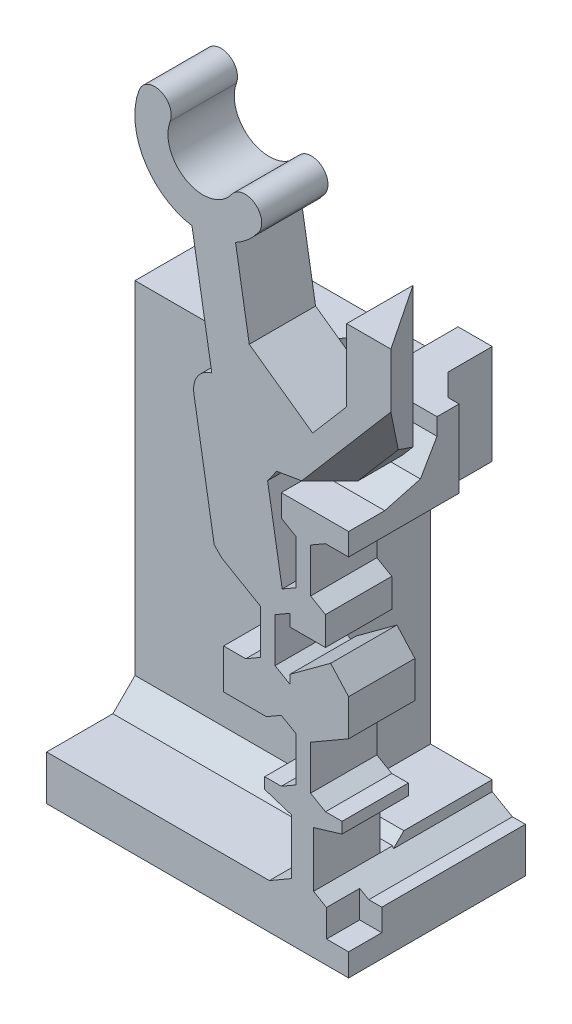
SolidWorks part; units mm, degrees
ref_plane "Front Plane" through (0, 0, 0) normal (0, 0, 1) x (1, 0, 0)
ref_plane "Top Plane" through (0, 0, 0) normal (0, 1, 0) x (1, 0, 0)
ref_plane "Right Plane" through (0, 0, 0) normal (1, 0, 0) x (0, 0, -1)
sketch "Sketch-SkeletonConfigUp" plane through (0, 0, 0) normal (0, 0, 1) x (1, 0, 0)
  line L0 (0, 0) -> (0, -50000) construction
  line L1 (0, 0) -> (4.5811, 6.2164) construction
  line L2 (9.8143, 13.3177) -> (4.5811, 13.945) construction
  line L3 (4.5811, 13.945) -> (2.9713, 10.4094) construction
  line L4 (2.9713, 10.4094) -> (4.5811, 6.2164) construction
  line L5 (4.5811, 13.945) -> (6.2429, 19.1409) construction
  line L6 (2.9713, 10.4094) -> (0.0405, 27.8193) construction
  line L7 (4.5811, 6.2164) -> (9.8143, 13.3177) construction
  line L8 (-587.3593, -797.0242) -> (9.8143, 13.3177) construction
  dimension "D2" = 7.7221
  dimension "D3" = 8.8212
  dimension "D4" = 5.2707
  dimension "D5" = 119.553
  dimension "D6" = 3.8848
  dimension "D7" = 5.4552
  dimension "D8" = 17.6549
  dimension "D9" = 4.4914
  dimension "D10" = 6.745
  dimension "D11" = 145.964
  dimension "D12" = 143.612
sketch "Sketch-SkeletonConfigDown" plane through (0, 0, 0) normal (0, 0, 1) x (1, 0, 0)
  line L0 (0, 0) -> (0, -50000) construction
  line L1 (0, 0) -> (4.5811, 6.2164) construction
  line L2 (9.8143, 13.3177) -> (4.5811, 13.945) construction
  line L3 (4.5811, 13.945) -> (6.1909, 10.4094) construction
  line L4 (6.1909, 10.4094) -> (4.5811, 6.2164) construction
  line L5 (4.5811, 13.945) -> (1.753, 18.6098) construction
  line L6 (6.1909, 10.4094) -> (-8.8652, 19.6294) construction
  line L7 (4.5811, 6.2164) -> (9.8143, 13.3177) construction
  line L8 (-589.9357, -800.5203) -> (9.8143, 13.3177) construction
  dimension "D2" = 7.7221
  dimension "D3" = 8.8212
  dimension "D4" = 5.2707
  dimension "D5" = 119.553
  dimension "D6" = 3.8848
  dimension "D7" = 5.4552
  dimension "D8" = 17.6549
  dimension "D9" = 4.4914
  dimension "D10" = 6.745
  dimension "D11" = 145.964
  dimension "D1" = 143.612
ref_plane "Plane-Cam Base" through (9.128, 0, 0) normal (1, 0, 0) x (0, 0, -1)
ref_plane "Plane-Down-to-Up Derailleur Clearance" through (6.628, 0, 0) normal (1, 0, 0) x (0, 0, -1)
ref_plane "Plane-Cam Cavity Roof" through (5.128, 0, 0) normal (1, 0, 0) x (0, 0, -1)
sketch "Sketch-SwitchBossUp" plane through (0, 0, 0) normal (0, 0, 1) x (1, 0, 0)
  line L0 (3.5811, 11.4759) -> (3.5811, 12.945) construction
  line L2 (6.5405, 21.1774) -> (6.5405, 24.4384)
  line L3 (6.5405, 24.4384) -> (8.5405, 24.4384)
  line L4 (8.5405, 24.4384) -> (8.5405, 20.4384)
  line L5 (5.5811, 12.5552) -> (5.5811, 11.263)
  line L7 (1.5115, 25.1048) -> (2.5464, 18.9575)
  line L8 (-0.4607, 24.7728) -> (0.4359, 19.4465)
  line L9 (2.9713, 10.4094) -> (0.0405, 27.8193) construction
  line L11 (-0.0396, 22.2712) -> (1.9326, 22.6032) construction
  line L15 (6.628, -23.7286) -> (6.628, 23.7286) construction
  line L16 (2.9713, 10.4094) -> (4.5811, 6.2164) construction
  line L17 (3.5811, 12.945) -> (3.5811, 14.945) construction
  line L18 (5.5811, 12.945) -> (5.5811, 14.945) construction
  line L19 (4.2561, 13.945) -> (4.9061, 13.945) construction
  line L20 (3.5811, 14.945) -> (5.5811, 14.945) construction
  line L21 (3.5811, 12.945) -> (5.5811, 12.945) construction
  line L22 (4.5811, 12.945) -> (4.5811, 14.945) construction
  line L23 (4.5811, 6.2164) -> (8.5405, 7.1023) construction
  line L24 (1.9713, 9.4094) -> (1.9713, 11.4094) construction
  line L25 (3.9713, 9.4094) -> (3.9713, 11.4094) construction
  line L26 (3.9713, 9.4094) -> (1.9713, 9.4094) construction
  line L27 (1.9713, 11.4094) -> (3.9713, 11.4094) construction
  line L28 (3.5811, 7.2164) -> (5.5811, 7.2164) construction
  line L29 (3.5811, 7.2164) -> (3.5811, 5.2164) construction
  line L30 (5.5811, 7.2164) -> (5.5811, 5.2164) construction
  line L31 (3.5811, 5.2164) -> (5.5811, 5.2164) construction
  line L32 (4.9061, 6.2164) -> (4.2561, 6.2164) construction
  line L40 (3.2963, 10.4094) -> (2.6463, 10.4094) construction
  line L43 (2.874, 4.5093) -> (0.7934, 4.5093) construction
  line L46 (5.0405, 1.437) -> (5.0405, 3.937)
  line L51 (4.9929, 19.3693) -> (2.5464, 18.9575)
  line L66 (0.0405, 27.8193) -> (0.0405, 50027.8193) construction
  line L74 (0.5455, 12.7717) -> (-0.3728, 18.2264)
  line L75 (0.3841, 13.7302) -> (2.3564, 14.0622) construction
  line L76 (5.5811, 11.263) -> (5.5811, 12.5552) construction
  line L77 (5.5811, 7.6061) -> (6.628, 8.2105)
  line L80 (5.8152, 10.763) -> (6.628, 9.8603)
  line L81 (8.5405, 1033.6218) -> (8.5405, 20.4384) construction
  line L82 (2.5464, 18.9575) -> (3.5585, 12.945) construction
  line L83 (3.6203, 12.5779) -> (2.8784, 16.9852)
  line L84 (2.8784, 16.9852) -> (6.0405, 17.5175)
  line L85 (6.9307, 9.5241) -> (8.5405, 7.7363) construction
  line L88 (3.5811, 16.3347) -> (6.8573, 16.3347)
  line L92 (3.7762, 8.3129) -> (6.9307, 9.5241) construction
  line L93 (6.3311, 4.3267) -> (5.0405, 3.937)
  line L95 (2.5464, 18.9575) -> (2.8784, 16.9852) construction
  line L96 (2.7124, 17.9713) -> (8.5405, 18.9524) construction
  line L97 (2.7124, 17.9713) -> (1.7262, 17.8053) construction
  line L98 (1.9713, 9.0197) -> (0.9713, 9.0197)
  line L99 (0.9713, 9.0197) -> (0.9713, 7.2164)
  line L100 (0.9713, 7.2164) -> (2.9061, 7.2164)
  line L101 (4.5811, 6.2164) -> (6.9307, 9.5241) construction
  line L103 (0.0405, 27.8193) -> (1.9448, 26.4638) construction
  line L104 (6.9307, 9.5241) -> (8.5405, 7.7363) construction
  line L106 (13.4416, 14.945) -> (5.5811, 14.945) construction
  line L107 (1.9713, 9.4094) -> (1.9713, 9.0197) construction
  line L109 (0.0405, 27.8193) -> (-2.1498, 28.6358) construction
  line L110 (8.5405, 20.4384) -> (6.0405, 17.5175)
  line L111 (6.628, 9.8603) -> (6.628, 8.2105)
  line L112 (6.628, 9.8603) -> (6.9307, 9.5241) construction
  line L113 (2.8311, 4.8267) -> (2.8311, 4.3267)
  line L114 (7.3693, 7.7363) -> (7.3563, 7.7363) construction
  line L115 (6.8573, 16.3347) -> (13.4416, 16.3347)
  line L116 (13.4416, 16.3347) -> (13.4416, -1.1653)
  line L117 (13.4416, -1.1653) -> (5.0405, -1.1653)
  line L119 (10.4375, 14.0252) -> (10.4375, 2.1692)
  line L121 (5.0405, -1.1653) -> (5.0405, 1.437) construction
  line L122 (8.237, 12.8031) -> (10.8393, 12.8031) construction
  line L123 (10.8393, 12.8031) -> (13.4416, 12.8031) construction
  line L124 (10.4375, 2.1692) -> (9.128, 0.8597)
  line L125 (8.5405, 7.5847) -> (13.4416, 7.5847) construction
  line L127 (5.5811, 15.3347) -> (5.5811, 14.945) construction
  line L130 (6.0405, 0.8597) -> (9.128, 0.8597)
  line L132 (2.8311, 4.3267) -> (4.0405, 3.937)
  line L133 (2.9713, 10.4094) -> (6.1909, 10.4094) construction
  line L134 (4.5811, 10.4094) -> (4.5811, 13.945) construction
  line L135 (4.5811, 10.4094) -> (4.5811, 6.2164) construction
  line L136 (0.8973, 12.4192) -> (0.5455, 12.7717)
  line L137 (3.9713, 9.4094) -> (5.5811, 7.2164) construction
  line L139 (5.8152, 10.763) -> (3.9713, 9.4094)
  line L140 (4.0405, 3.937) -> (4.0405, 1.437)
  line L141 (4.0405, 1.437) -> (3.0405, 0.8597)
  line L142 (3.0405, 0.8597) -> (3.0405, -1.1653)
  line L143 (8.5405, 20.4384) -> (8.5405, 18.9524) construction
  line L145 (8.5405, 17.9384) -> (8.5405, -49992.0368) construction
  line L147 (5.5811, 11.263) -> (5.5811, 12.5552) construction
  line L149 (6.3311, 4.8267) -> (6.3311, 4.3267)
  line L150 (3.0405, -1.1653) -> (5.0405, -1.1653)
  line L151 (4.0405, 3.937) -> (5.0405, 3.937) construction
  line L152 (4.2561, 14.945) -> (4.2561, 12.945)
  line L153 (4.9061, 14.945) -> (4.9061, 12.945)
  line L155 (4.2561, 14.945) -> (3.5811, 15.3347)
  line L156 (4.9061, 14.945) -> (5.5811, 15.3347)
  line L157 (3.5811, 16.3347) -> (3.5811, 15.3347)
  line L158 (5.5811, 15.3347) -> (9.128, 15.3347)
  line L162 (3.2963, 11.4094) -> (3.2963, 9.4094)
  line L164 (2.6463, 11.4094) -> (2.6463, 9.4094)
  line L169 (4.2561, 7.2164) -> (4.2561, 5.2164)
  line L170 (4.9061, 5.2164) -> (4.9061, 7.2164)
  line L175 (4.2561, 7.2164) -> (3.5811, 7.6061)
  line L176 (4.9061, 7.2164) -> (5.5811, 7.6061)
  line L177 (5.5811, 7.2164) -> (5.5811, 7.6061) construction
  line L179 (4.2561, 5.2164) -> (3.5811, 4.8267)
  line L180 (3.5811, 5.2164) -> (3.5811, 4.8267) construction
  line L181 (3.5811, 4.8267) -> (2.8311, 4.8267)
  line L183 (4.9061, 5.2164) -> (5.5811, 4.8267)
  line L184 (5.5811, 5.2164) -> (5.5811, 4.8267) construction
  line L186 (9.128, -23.7286) -> (9.128, 23.7286) construction
  line L187 (2.6463, 9.4094) -> (1.9713, 9.0197)
  line L188 (3.2963, 9.4094) -> (3.9713, 9.0197)
  line L189 (3.2963, 11.4094) -> (3.9713, 11.7991)
  line L190 (2.6463, 11.4094) -> (0.8973, 12.4192)
  line L191 (3.9713, 11.4094) -> (3.9713, 11.7991) construction
  line L192 (3.9713, 11.7991) -> (3.9713, 11.263)
  line L193 (4.9061, 12.945) -> (5.5811, 12.5552)
  line L194 (4.2561, 12.945) -> (3.6203, 12.5779)
  line L195 (3.9713, 11.263) -> (5.5811, 11.263)
  line L196 (3.9713, 9.4094) -> (3.9713, 9.0197)
  line L197 (3.5811, 7.2164) -> (3.5811, 7.6061) construction
  line L199 (3.5811, 7.6061) -> (2.9061, 7.2164)
  line L200 (5.5811, 4.8267) -> (6.3311, 4.8267)
  line L201 (2.8311, 4.3267) -> (2.8311, 3.937) construction
  line L202 (2.8311, 3.937) -> (4.0405, 3.937) construction
  line L203 (10.4375, 14.0252) -> (9.128, 15.3347)
  line L204 (4.0405, 1.437) -> (3.0405, 1.437) construction
  line L205 (3.0405, 1.437) -> (3.0405, 0.8597) construction
  line L206 (5.0405, 1.437) -> (6.0405, 0.8597)
  line L207 (8.5405, 18.9524) -> (8.5405, 17.9384) construction
  line L208 (6.0405, 17.5175) -> (8.5405, 17.9384) construction
  line L209 (8.5405, 20.4384) -> (8.5405, 17.9384) construction
  line L210 (6.5405, 21.1774) -> (4.9929, 19.3693)
  arc A0 (1.5115, 25.1048) -> (2.5558, 26.0289) centre (0.0405, 27.8193) ccw
  arc A1 (-0.4607, 24.7728) -> (-2.8525, 28.8978) centre (0.0405, 27.8193) cw
  arc A2 (-2.8525, 28.8978) -> (-1.447, 28.3738) centre (-2.1498, 28.6358) cw
  arc A3 (2.5558, 26.0289) -> (1.3338, 26.8987) centre (1.9448, 26.4638) ccw
  arc A4 (-1.447, 28.3738) -> (1.3338, 26.8987) centre (0.0405, 27.8193) ccw
  arc A5 (3.5811, 12.945) -> (3.5811, 14.945) centre (3.1778, 13.945) ccw construction
  arc A6 (5.5811, 12.945) -> (5.5811, 14.945) centre (5.9843, 13.945) cw construction
  arc A7 (2.5293, 9.921) -> (1.9713, 11.4094) centre (1.568, 10.4094) ccw construction
  arc A8 (3.9713, 11.4094) -> (3.9713, 9.4094) centre (4.3745, 10.4094) ccw construction
  arc A9 (3.5811, 7.2164) -> (3.5811, 5.2164) centre (3.1779, 6.2164) cw construction
  arc A10 (5.5811, 7.2164) -> (5.5811, 5.2164) centre (5.9844, 6.2164) ccw construction
  arc A19 (-0.3728, 18.2264) -> (0.4359, 19.4465) centre (0.6836, 18.4042) cw
  circle A28 centre (0.0405, 27.8193) radius 2.3375 construction
  arc A29 (1.9713, 9.4094) -> (2.5293, 9.921) centre (1.568, 10.4094) ccw construction
  point P53 (4.5811, 13.945)
  point P63 (2.9713, 10.4094)
  point P93 (0.9465, 22.4372)
  dimension "D23" = 1.5875
  dimension "D24" = 0.75
  dimension "D2" = 2
  dimension "D5" = 2
  dimension "D6" = 0.65
  dimension "D8" = 42
  dimension "D7" = 2
  dimension "D10" = 5
  dimension "D11" = 8.5
  dimension "D14" = 7.5
  dimension "D4" = 3
  dimension "D16" = 42
  dimension "D12" = 1
  dimension "D13" = 2.5
  dimension "D25" = 120
  dimension "D26" = 120
  dimension "D27" = 120
  dimension "D28" = 120
  dimension "D29" = 120
  dimension "D30" = 120
  dimension "D31" = 120
  dimension "D32" = 120
  dimension "D33" = 120
  dimension "D34" = 120
  dimension "D35" = 120
  dimension "D36" = 120
  dimension "D17" = 0.5
  dimension "D20" = 3.5
  dimension "D21" = 1
  dimension "D18" = 45
  dimension "D9" = 17.5
  dimension "D22" = 1
  dimension "D19" = 120
  dimension "D37" = 120
  dimension "D15" = 45
  dimension "D38" = 2
  dimension "D39" = 0.5
  dimension "D40" = 60
  dimension "D41" = 1
  dimension "D42" = 45
  dimension "D43" = 120
  dimension "D44" = 2
  dimension "D45" = 2.5
  dimension "D46" = 2.5
  dimension "D47" = 4
  dimension "D48" = 2
extrude "Boss-Switch Main" add sketch "Sketch-SwitchBossUp" along normal blind 3
sketch "Sketch1" plane through (0, 0, 0) normal (0, 0, -1) x (-1, 0, 0)
  line L0 (-3.5811, 16.3347) -> (-3.5811, 15.3347) construction
  line L1 (-7.5811, -1.1653) -> (0.4122, -1.1653)
  line L2 (-7.5811, -1.1653) -> (-7.5811, 0.8597)
  line L4 (0.4122, -1.1653) -> (0.4122, 0.8597)
  line L5 (-3.5811, 18.8347) -> (-7.5811, 18.8347)
  line L10 (-7.5811, 18.8347) -> (-7.5811, 15.3347)
  line L11 (-4.0405, 1.437) -> (-5.0405, 1.437)
  line L12 (-7.5811, 15.3347) -> (-3.5811, 15.3347)
  line L13 (-4.0405, 1.437) -> (-3.0405, 0.8597)
  line L14 (-3.5811, 15.3347) -> (-3.5811, 18.8347)
  line L22 (-3.0405, -1.1653) -> (-13.4416, -1.1653) construction
  line L23 (-3.0405, 0.8597) -> (0.4122, 0.8597)
  line L24 (-5.0405, 1.437) -> (-6.0405, 0.8597)
  line L25 (-6.0405, 0.8597) -> (-7.5811, 0.8597)
  line L26 (-9.128, 15.3347) -> (-5.5811, 15.3347) construction
  dimension "D1" = 3.5
  dimension "D4" = 4
extrude "Boss-Flange Width" add sketch "Sketch1" along normal blind 5
ref_plane "Plane-Sta2Sit Groove" through (0.0405, 0, 0) normal (1, 0, 0) x (0, 0, -1)
ref_plane "Plane-Cam Outer Surface" through (-12.0395, 0, 0) normal (1, 0, 0) x (0, 0, -1)
ref_plane "Plane-FlangeTop" through (-7.0395, 0, 0) normal (1, 0, 0) x (0, 0, -1)
sketch "Sketch2" plane through (-7.0395, 0, 0) normal (1, 0, 0) x (0, 0, -1)
  line L0 (5, 15.3347) -> (0, 15.3347) construction
  line L1 (5, 17.3347) -> (1, 17.3347)
  line L2 (5, 17.3347) -> (5, 15.3347)
  line L3 (5, 15.3347) -> (1, 15.3347)
  line L4 (1, 17.3347) -> (1, 15.3347)
  line L10 (-3, -1.1653) -> (-3, 16.3347) construction
  line L11 (5, 0.8597) -> (-3, 0.8597)
  line L12 (5, 0.8597) -> (5, -1.1653)
  line L13 (5, -1.1653) -> (-3, -1.1653)
  line L14 (-3, 0.8597) -> (-3, -1.1653)
  line L15 (0, 10.4094) -> (0, 27.8193) construction
  line L17 (5, 0.8597) -> (5, -1.1653) construction
  line L18 (-3, 0.8597) -> (0, 0.8597) construction
  dimension "D1" = 1
  dimension "D2" = 2
extrude "Boss-Flange Height" add sketch "Sketch2" along normal up to surface (11.6675 mm away)
sketch "Sketch10" plane through (0, 15.3347, 0) normal (0, 1, 0) x (1, 0, 0)
  line L0 (9.128, -23.7286) -> (9.128, 23.7286) construction
  line L1 (7.5811, 5) -> (5.128, 5)
  line L2 (7.5811, 5) -> (7.5811, 2)
  line L3 (7.5811, 2) -> (5.128, 2)
  line L5 (4.628, 7) -> (4.628, 1) construction
  line L6 (3.5811, 1) -> (-7.0395, 1) construction
  line L8 (5.128, 5) -> (5.128, 2)
  dimension "D1" = 1
  dimension "D2" = 0.5
  dimension "D3" = 4.5
extrude "Cut-Up-To-Down Derailleur Clearance" cut sketch "Sketch10" along normal up to next
sketch "Sketch17" plane through (0, 15.3347, 0) normal (0, -1, 0) x (1, 0, 0)
  line L0 (5.128, -5) -> (-7.0395, -5)
  line L1 (5.128, -5) -> (3.5811, -5) construction
  line L2 (-7.0395, -5) -> (-7.0395, -1)
  line L3 (-7.0395, -1) -> (5.128, -1)
  line L4 (5.128, -1) -> (5.128, -5)
  line L5 (-7.0395, -1) -> (-7.0395, -5) construction
extrude "Boss-Flange Support" add sketch "Sketch17" along normal up to surface (14.475 mm away) up to face at (-1.9995, 0.8597, -1)
sketch "Sketch-HolePositions" plane through (0, -1.1653, 0) normal (0, -1, 0) x (1, 0, 0)
  line L0 (-7.0395, -3) -> (7.5811, -3) construction
  line L1 (7.5811, -5) -> (-7.0395, -5) construction
  line L2 (7.5811, -5) -> (7.5811, 0) construction
  line L4 (-7.0395, -22.2167) -> (-7.0395, 22.2167) construction
  line L5 (3.5811, -1) -> (3.5811, -5) construction
  point P6 (-4.0395, -3)
  point P7 (0.5811, -3)
  dimension "D1" = 3
  dimension "D2" = 3
  dimension "D3" = 2
sketch "Sketch6" plane through (0, -1.1653, 0) normal (0, -1, 0) x (-1, 0, 0)
  point P0 (4.0395, 3)
  point P3 (-0.5811, 3)
hole_wizard "Tap Drill for M2x0.4 Tap1" positions "Sketch6" profile "Sketch5" hole size "M2x0.4" standard "ANSI Metric" end condition through all
sketch "Sketch5" plane through (-4.0395, -1.1653, -3) normal (1, 0, 0) x (0, 0, -1)
  line L0 (0, 0) -> (0, 30.5511)
  line L1 (0, 30.5511) -> (0.8, 30.5511)
  line L2 (0.8, 30.5511) -> (0.8, 0)
  line L5 (0.8, 0) -> (0, 0)
  line L11 (0, -6.35) -> (0, 107.95) construction
  dimension "Thru Hole Dia." = 1.6
  dimension "Thru Hole Depth" = 30.5511
sketch "Sketch9" plane through (0, -1.1653, 0) normal (0, -1, 0) x (1, 0, 0)
  point P0 (-4.0395, -3)
  point P3 (0.5811, -3)
hole_wizard "M2 Clearance Hole2" positions "Sketch9" profile "Sketch8" hole size "M2" standard "ANSI Metric"
sketch "Sketch8" plane through (-4.0395, -1.1653, -3) normal (1, 0, 0) x (0, 0, -1)
  line L0 (0, 0) -> (0, 15.721)
  line L1 (0, 15.721) -> (1.2, 15)
  line L2 (1.2, 15) -> (1.2, 0)
  line L5 (1.2, 0) -> (0, 0)
  line L10 (0, 15.721) -> (-1.2, 15) construction
  line L11 (0, -6.35) -> (0, 107.95) construction
  dimension "Hole Dia." = 2.4
  dimension "Hole Depth" = 15
  dimension "Drill Angle" = 118
sketch "Sketch-Measurements for Derailleur Ramps" plane through (0, 0, 0) normal (0, 0, 1) x (1, 0, 0)
  line L0 (2.8784, 16.9852) -> (2.5464, 18.9575)
  line L1 (2.7124, 17.9713) -> (1.7262, 17.8053)
  line L2 (2.9713, 10.4094) -> (0.0405, 27.8193) construction
  line L3 (1.7262, 17.8053) -> (-1.8937, 15.3603)
  line L4 (6.1909, 10.4094) -> (-8.8652, 19.6294) construction
  line L5 (1.7262, 17.8053) -> (2.6012, 12.6077)
  line L6 (2.6012, 12.6077) -> (-1.8937, 15.3603)
  line L7 (-0.0837, 16.5828) -> (-0.0837, 17.8053)
  line L8 (-0.0837, 17.8053) -> (1.7262, 17.8053)
  line L9 (6.1909, 10.4094) -> (2.9713, 10.4094)
  line L10 (5.386, 8.3129) -> (3.7762, 8.3129)
  line L12 (6.1909, 10.4094) -> (4.5811, 6.2164) construction
  line L13 (4.5811, 8.3129) -> (4.5811, 8.7912)
  line L14 (4.5811, 6.2164) -> (5.386, 8.3129)
  line L15 (2.9713, 10.4094) -> (4.5811, 6.2164) construction
  line L16 (3.7762, 8.3129) -> (4.5811, 6.2164)
  line L17 (5.386, 8.3129) -> (5.386, 8.7912)
  dimension "D1" = 1.81
  dimension "D2" = 0.8049
sketch "Sketch12" plane through (0, 24.4384, 0) normal (0, 1, 0) x (1, 0, 0)
  line L0 (6.5405, 0) -> (8.5405, -3)
  line L1 (8.5405, -3) -> (8.5405, 0)
  line L2 (8.5405, 0) -> (6.5405, 0)
extrude "Cut-Up-to-Down Cantilever Slope" cut sketch "Sketch12" against normal up to next
ref_plane "Plane1" through (0, 7.1023, 0) normal (0, 1, 0) x (1, 0, 0)
sketch "Sketch-Derailleur Location" plane through (0, 7.1023, 0) normal (0, 1, 0) x (1, 0, 0)
  line L0 (8.5405, 0) -> (8.5405, -3)
  line L1 (4.0405, -3) -> (3.0405, -3) construction
  line L2 (-119237.4187, 0) -> (9.8143, 0) construction
  point P0 (8.5405, 0)
  point P8 (8.5405, -1.5)
ref_plane "Plane-Cantilever Cut" [suppressed] through (7.0848, 8.5204, -1.9058) normal (-0.6301, -0.7578, 0.1695) x (-0.7765, 0.6151, -0.1368)
sketch "Sketch14" [suppressed] plane through (7.0848, 8.5204, -1.9058) normal (-0.6301, -0.7578, 0.1695) x (-0.7765, 0.6151, -0.1368)
  line L0 (2.3023, -1.6911) -> (-0.3551, -1.6911)
  line L2 (2.3023, -4.3362) -> (2.3023, -1.6911)
  line L3 (-0.3551, -1.6911) -> (-0.3551, -4.4608)
  line L5 (-0.3551, -4.4608) -> (1.0087, -5.0843)
  line L6 (1.0087, -5.0843) -> (2.3023, -4.3362)
extrude "Cut-Down-to-Up Cantilever Slope" [suppressed] cut sketch "Sketch14" against normal up to next
sketch "Sketch16" plane through (0, 0, 0) normal (0, 0, -1) x (-1, 0, 0)
  line L0 (-7.5811, 18.8347) -> (-13.4416, 18.8347)
  line L1 (-13.4416, 18.8347) -> (-13.4416, -1.1653)
  line L2 (-13.4416, -1.1653) -> (-6.628, -1.1653)
  line L3 (-13.4416, -1.1653) -> (-5.0405, -1.1653) construction
  line L4 (-6.628, -1.1653) -> (-6.628, 5.2038)
  line L5 (-6.628, 5.2038) -> (-8.0037, 5.2038)
  line L6 (-8.0037, 5.2038) -> (-8.0037, 12.0484)
  line L7 (-8.0037, 12.0484) -> (-6.628, 12.0484)
  line L8 (-6.628, 12.0484) -> (-6.628, 17.9477)
  line L9 (-6.628, 23.7286) -> (-6.628, -23.7286) construction
  line L10 (-3.5811, 18.8347) -> (-6.5405, 18.8347) construction
  line L11 (-7.5811, 18.8347) -> (-6.628, 17.9477)
extrude "Cut-Down-to-Up Derailleur Clearance" cut sketch "Sketch16" against normal through all and the other way through all
ref_plane "Plane-Symmetry Plane" through (0, 0, 1.5) normal (0, 0, 1) x (1, 0, 0)
sketch "Sketch-Cable Center Point" plane through (0, 0, 1.5) normal (0, 0, 1) x (1, 0, 0)
  line L0 (0.0405, 27.8193) -> (0.1722, 27.0366)
  line L1 (2.9713, 10.4094) -> (0.0405, 27.8193) construction
  point P0 (0.0405, 27.8193)
  dimension "D1" = 0.7937
chamfer "Chamfer-Flange Support" distance 1.5 angle 45 1 edges at (3.5811, 17.3347, -3)
chamfer "Chamfer-Flange Support 2" distance 1 angle 45 2 edges at (5.128, 17.0847, -2) (5.128, 15.3347, -1.5)
chamfer "Chamfer-Flange Support 3" distance 1 angle 45 1 edges at (-1.9995, 0.8597, -1)
sketch "Sketch18" plane through (6.628, 0, 0) normal (1, 0, 0) x (0, 0, -1)
  line L1 (-3, -0.1403) -> (-1.5, -0.1403)
  line L2 (-3, -0.1403) -> (-3, 1.437)
  line L3 (-3, 1.437) -> (-1.5, 1.437)
  line L4 (-1.5, -0.1403) -> (-1.5, 1.437)
  line L5 (0.5774, 1.437) -> (0, 1.437) construction
  line L6 (-3, -1.1653) -> (-3, 0.8597) construction
  line L7 (-3, 0.8597) -> (5, 0.8597) construction
  dimension "D1" = 1.5
  dimension "D2" = 1
extrude "Cut-Down-to-Up Derailleur Clearance 2" cut sketch "Sketch18" against normal blind 1
sketch "Sketch19" plane through (0, 0, 0) normal (0, 0, 1) x (1, 0, 0)
  line L7 (3.5811, 18.8347) -> (6.628, 18.8347)
  line L8 (6.628, 18.8347) -> (6.628, 16.3347)
  line L9 (6.628, 16.3347) -> (3.5811, 16.3347)
  line L10 (3.5811, 16.3347) -> (3.5811, 18.8347)
  line L11 (6.628, 16.3347) -> (6.628, 17.9477) construction
extrude "Cut-Up-to-Down Cantilever Clearance" cut sketch "Sketch19" against normal up to surface (1 mm away) up to face at (1.4435, 12.7784, -1)
chamfer "Chamfer1" distance 1 angle 60 1 edges at (5.1045, 16.3347, -1) first distance on face at (5.1045, 16.3347, 1)
chamfer "Chamfer3" distance 0.75 angle 60 1 edges at (3.5811, 16.7007, -1) first distance on face at (3.5811, 16.1233, 0.6667)
chamfer "Chamfer4" distance 0.5 angle 60 1 edges at (4.205, 15.3347, -1) first distance on face at (5.1242, 15.3347, -0.0278)
chamfer "Chamfer5" distance 0.5 angle 45 1 edges at (2.8784, 16.9852, 1.5)
chamfer "Chamfer6" distance 2.5 angle 45 1 edges at (2.5464, 18.9575, 1.5)
chamfer "Chamfer7" distance 1 angle 45 1 edges at (7.2905, 18.978, 3)
sketch "Sketch22" plane through (0, 0, 0) normal (0, 0, 1) x (1, 0, 0)
  line L0 (6.628, 17.9477) -> (7.5811, 18.8347) construction
  line L1 (6.628, 18.8347) -> (7.5811, 18.8347) construction
  line L2 (6.628, 17.9477) -> (6.628, 18.8347) construction
  line L3 (6.628, 17.9477) -> (7.5811, 18.8347)
  line L4 (6.628, 18.8347) -> (7.5811, 18.8347)
  line L5 (6.628, 17.9477) -> (6.628, 18.8347)
extrude "Cut-Extrude3" cut sketch "Sketch22" against normal up to next
chamfer "Chamfer8" distance 0.5 angle 45 1 edges at (5.1045, 16.3347, 0) first distance on face at (4.2965, 17.2286, -0.5161)
sketch "Sketch23" plane through (0, 0, -1) normal (0, 0, 1) x (1, 0, 0)
  line L0 (5.128, 1.8597) -> (2.3369, 1.8597)
  line L1 (-7.0395, 1.8597) -> (5.128, 1.8597) construction
  line L2 (2.3369, 1.8597) -> (2.3369, 14.3347)
  line L3 (2.3369, 14.3347) -> (5.128, 14.3347)
  line L4 (5.128, 14.3347) -> (5.128, 1.8597)
  point P5 (5.262, 14.4686)
  point P9 (5.128, 14.3347)
extrude "Cut-Extrude4" cut sketch "Sketch23" against normal through all
equation "\"axle-diameter\"=2"
equation "\"switch-thickness\"=12"
equation "\"base-width\"=4.0"
equation "\"axle-bushing-radius\"=3"
equation "\"clearance\"= 0.25"
equation "\"arm-width\"=1.5"
equation "\"min-diameter\"=70"
equation "\"alpha\"=143.6120"
equation "\"gamma\"=119.5526"
equation "\"delta\"=145.9637"
equation "\"epsilon\"=6.7452"
equation "\"l_AB\"=8.8212"
equation "\"l_AC\"=4.4914"
equation "\"l_BD\"=5.2707"
equation "\"l_CD\"=3.8848"
equation "\"l_CE\"=17.6549"
equation "\"l_DF\"=5.4552"
equation "\"l_OA\"=7.7221"
equation "\"D2@Sketch-SkeletonConfigUp\" = \"l_OA\""
equation "\"D3@Sketch-SkeletonConfigUp\" = \"l_AB\""
equation "\"D4@Sketch-SkeletonConfigUp\" = \"l_BD\""
equation "\"D5@Sketch-SkeletonConfigUp\" = \"gamma\""
equation "\"D6@Sketch-SkeletonConfigUp\" = \"l_CD\""
equation "\"D7@Sketch-SkeletonConfigUp\" = \"l_DF\""
equation "\"D8@Sketch-SkeletonConfigUp\" = \"l_CE\""
equation "\"D9@Sketch-SkeletonConfigUp\" = \"l_AC\""
equation "\"D_groove\"=3.175"
equation "\"D7@Sketch-SkeletonConfigDown\" = \"l_DF\""
equation "\"D6@Sketch-SkeletonConfigDown\" = \"l_CD\""
equation "\"D2@Sketch-SkeletonConfigDown\" = \"l_OA\""
equation "\"D3@Sketch-SkeletonConfigDown\" = \"l_AB\""
equation "\"D9@Sketch-SkeletonConfigDown\" = \"l_AC\""
equation "\"D8@Sketch-SkeletonConfigDown\" = \"l_CE\""
equation "\"D5@Sketch-SkeletonConfigDown\" = \"gamma\""
equation "\"D4@Sketch-SkeletonConfigDown\" = \"l_BD\""
equation "\"D1@Sketch-SkeletonConfigDown\" = \"alpha\""
equation "\"hinge_length\"=1.5"
equation "\"hinge_depth\"=0.25"
equation "\"D10@Sketch-SkeletonConfigUp\"=\"epsilon\""
equation "\"D11@Sketch-SkeletonConfigUp\"=\"delta\""
equation "\"D12@Sketch-SkeletonConfigUp\"=\"alpha\""
equation "\"D11@Sketch-SkeletonConfigDown\"=\"delta\""
equation "\"D10@Sketch-SkeletonConfigDown\"=\"epsilon\""
equation "\"EE_dx\"=8.9056"
equation "\"EE_dy\"=8.1898"
equation "\"r_groove\"=\"D_groove\"/2"
equation "\"t_wall\"=25.4/16"
equation "\"width_lower\"=\"D_groove\"+\"t_wall\""
equation "\"cable_to_bottom\"=30.6257"
equation "\"switch_EE-up_base_dy\"=24"
equation "\"switch_EE-down_base_dy\"=16"
equation "\"D_axle\"=25.4/8"
equation "\"D_up_to_down\"=16"
equation "\"D_down_to_up\"=25"
equation "\"t_cam_base\"=7.5"
equation "\"D23@Sketch-SwitchBossUp\"=\"D_groove\"/2"
equation "\"D1@Sketch-Cable Center Point\"=\"D_groove\"/4"
